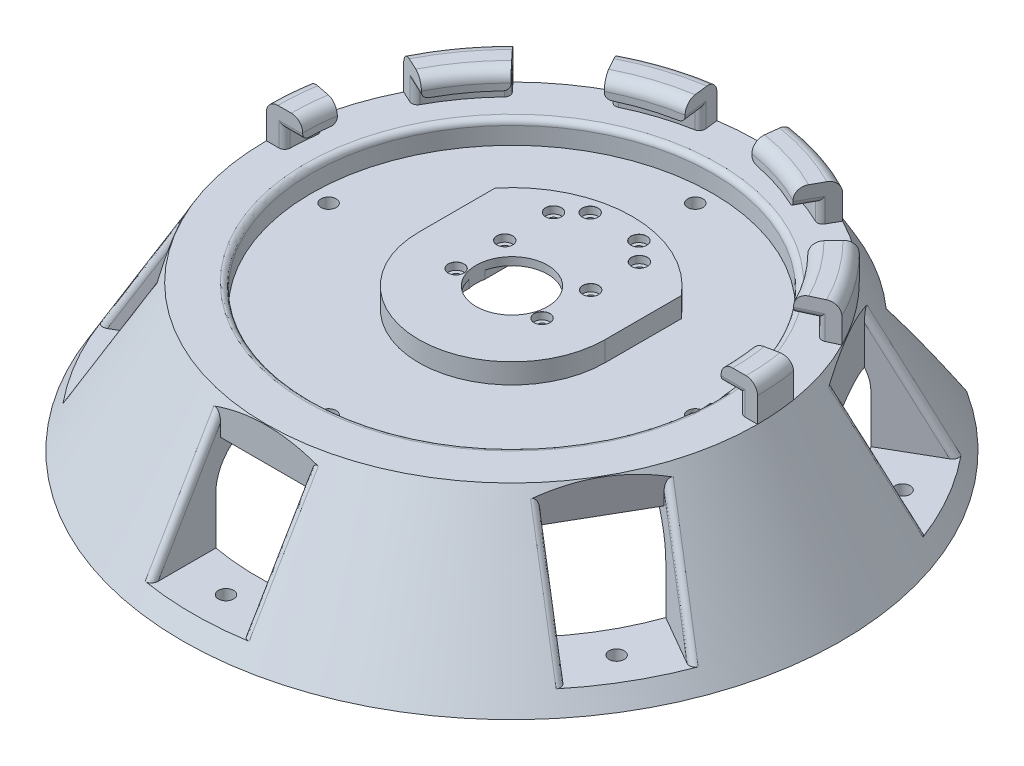
SolidWorks part; units mm, degrees
note: The reader was unsure of these and kept them because the rebuilt part matched: shared geometry of "Sketch3<3>".
material "PLA"
ref_plane "Front Plane" through (0, 0, 0) normal (0, 0, 1) x (1, 0, 0)
ref_plane "Top Plane" through (0, 0, 0) normal (0, 1, 0) x (1, 0, 0)
ref_plane "Right Plane" through (0, 0, 0) normal (1, 0, 0) x (0, 0, -1)
sketch "Sketch1" plane through (0, 0, 0) normal (0, 0, 1) x (1, 0, 0)
  line L0 (0, 0) -> (-85.725, 0)
  line L1 (-85.725, 0) -> (-115.0544, -50.8)
  line L2 (-115.0544, -50.8) -> (0, -50.8)
  line L6 (0, 0) -> (0, -50.8) construction
  line L7 (0, 0) -> (0, -50.8)
  dimension "D1" = 85.725
  dimension "D3" = 50.8
  dimension "D4" = 60
revolve "Revolve1" add sketch "Sketch1" angle 360 about L6
sketch "Sketch2" plane through (0, 0, 0) normal (0, 1, 0) x (1, 0, 0)
  circle A0 centre (0, 0) radius 12.5
  dimension "D1" = 25
extrude "Cut-Extrude1" cut sketch "Sketch2" against normal through all
sketch "Sketch3" plane through (0, 0, 0) normal (0, 1, 0) x (1, 0, 0)
  line L0 (-32.5, 0) -> (-32.5, 26.6036)
  line L1 (-32.5, 26.6036) -> (32.5, 26.6036)
  line L2 (32.5, 26.6036) -> (32.5, 0)
  circle A0 centre (0, 0) radius 32.5
  circle A1 centre (0, 0) radius 70
  circle A2 centre (0, 0) radius 42
  circle M1 centre (0, 0) radius 12.5
  dimension "D1" = 65
  dimension "D2" = 140
  dimension "D3" = 84
extrude "Cut-Extrude2" cut sketch "Sketch3" against normal blind 8 contours A1 A0 L0 L1 L2 | A1 A2
sketch "Sketch7" plane through (0, -50.8, 0) normal (0, -1, 0) x (1, 0, 0)
  line L0 (0, 88.9) -> (0, -161.1) construction
  line L1 (-85.4, 0) -> (85.4, 0) construction
  line L2 (-60, -65.5989) -> (-60, -161.1)
  line L3 (-60, -161.1) -> (60, -161.1)
  line L4 (60, -161.1) -> (60, -65.5989)
  line L5 (-60, -65.5989) -> (60, -65.5989) construction
  arc A2 (60, -65.5989) -> (-60, -65.5989) centre (0, 0) ccw
  dimension "D1" = 177.8
  dimension "D2" = 25.4
  dimension "D3" = 25.4
  dimension "D4" = 120
  dimension "D5" = 250
extrude "Cut-Extrude5" cut sketch "Sketch7" against normal blind 39 contours L3 L4 A2 L2
sketch "Sketch8" plane through (0, 0, 0) normal (0, 1, 0) x (1, 0, 0)
  line L0 (0, 0) -> (0, -115.0544) construction
  line L2 (-15.875, -123.925) -> (15.875, -123.925)
  line L3 (-15.875, -123.925) -> (-15.875, -85.825)
  line L4 (-15.875, -85.825) -> (15.875, -85.825)
  line L5 (15.875, -123.925) -> (15.875, -85.825)
  line L6 (-15.875, -123.925) -> (15.875, -85.825) construction
  line L7 (-15.875, -85.825) -> (15.875, -123.925) construction
  arc A0 (-60, 98.1708) -> (60, 98.1708) centre (0, 0) ccw construction
  point P6 (0, -104.875)
  dimension "D1" = 85.825
  dimension "D2" = 38.1
  dimension "D3" = 31.75
extrude "Cut-Extrude6" cut sketch "Sketch8" against normal blind 44.45
pattern_circular "CirPattern2" count 6 over 360 about axis through (0, 0, 0) along (0, 1, 0) of "Cut-Extrude6"
sketch "Sketch9" plane through (0, 0, 0) normal (0, 1, 0) x (1, 0, 0)
  line L0 (0, 0) -> (0, -115.0544) construction
  arc A0 (-60, 98.1708) -> (60, 98.1708) centre (0, 0) ccw construction
  circle A1 centre (0, -99.8144) radius 2.65
  dimension "D1" = 5.3
  dimension "D2" = 15.24
extrude "Cut-Extrude7" cut sketch "Sketch9" against normal through all
pattern_circular "CirPattern3" count 6 over 360 about axis through (0, 0, 0) along (0, 1, 0) of "Cut-Extrude7"
sketch "Sketch12" plane through (0, 0, 0) normal (0, 0, 1) x (1, 0, 0)
  line L0 (85.725, 0) -> (85.725, 12.7)
  line L1 (85.725, 12.7) -> (73.025, 12.7)
  line L2 (73.025, 12.7) -> (73.025, 6.35)
  line L3 (73.025, 6.35) -> (79.375, 6.35)
  line L4 (79.375, 6.35) -> (79.375, 0)
  line L5 (85.725, 0) -> (-85.725, 0) construction
  line L6 (0, 0) -> (0, 12.7) construction
  line L7 (12.5, 0) -> (-12.5, 0) construction
  line L8 (79.375, 0) -> (85.725, 0)
  point P13 (0, 6.35)
  dimension "D1" = 6.35
  dimension "D2" = 73.025
  dimension "D3" = 79.375
  dimension "D4" = 12.7
  dimension "D5" = 12.7
revolve "Revolve2" add sketch "Sketch12" angle 180 about L6
sketch "Sketch15" plane through (0, -11.8, 0) normal (0, -1, 0) x (1, 0, 0)
  line L0 (0, -1000) -> (0, 49000) construction
  point P1 (-15, 4.5)
  point P4 (-15, -12.5)
  point P5 (-15, -29.5)
  point P6 (-8.5, -35.8)
  point P7 (8.5, -35.8)
  point P8 (15, -29.5)
  point P9 (15, -12.5)
  point P10 (15, 4.5)
  dimension "D1" = 17
  dimension "D2" = 17
  dimension "D3" = 4.5
  dimension "D4" = 15
  dimension "D5" = 8.5
  dimension "D6" = 35.8
sketch "Sketch18" plane through (0, 12.7, 0) normal (0, 1, 0) x (1, 0, 0)
  line L0 (46.6433, 89.7185) -> (70.9138, 72.0849)
  line L1 (0, 201000) -> (0, -249000) construction
  line L2 (-15, 100) -> (-9, 50)
  line L3 (-9, 50) -> (9, 50)
  line L4 (9, 50) -> (15, 100)
  line L5 (-15, 100) -> (15, 100)
  line L6 (36.6704, 35.1608) -> (70.9138, 72.0849)
  line L7 (22.1081, 45.7409) -> (36.6704, 35.1608)
  line L8 (46.6433, 89.7185) -> (22.1081, 45.7409)
  line L9 (90.4704, 45.1675) -> (99.7409, 16.6359)
  line L10 (50.334, 6.8913) -> (99.7409, 16.6359)
  line L11 (44.7717, 24.0104) -> (50.334, 6.8913)
  line L12 (90.4704, 45.1675) -> (44.7717, 24.0104)
  line L13 (99.7409, -16.6359) -> (90.4704, -45.1675)
  line L14 (44.7717, -24.0104) -> (90.4704, -45.1675)
  line L15 (50.334, -6.8913) -> (44.7717, -24.0104)
  line L16 (99.7409, -16.6359) -> (50.334, -6.8913)
  line L17 (70.9138, -72.0849) -> (46.6433, -89.7185)
  line L18 (22.1081, -45.7409) -> (46.6433, -89.7185)
  line L19 (36.6704, -35.1608) -> (22.1081, -45.7409)
  line L20 (70.9138, -72.0849) -> (36.6704, -35.1608)
  line L21 (15, -100) -> (-15, -100)
  line L22 (-9, -50) -> (-15, -100)
  line L23 (9, -50) -> (-9, -50)
  line L24 (15, -100) -> (9, -50)
  line L25 (-46.6433, -89.7185) -> (-70.9138, -72.0849)
  line L26 (-36.6704, -35.1608) -> (-70.9138, -72.0849)
  line L27 (-22.1081, -45.7409) -> (-36.6704, -35.1608)
  line L28 (-46.6433, -89.7185) -> (-22.1081, -45.7409)
  line L29 (-90.4704, -45.1675) -> (-99.7409, -16.6359)
  line L30 (-50.334, -6.8913) -> (-99.7409, -16.6359)
  line L31 (-44.7717, -24.0104) -> (-50.334, -6.8913)
  line L32 (-90.4704, -45.1675) -> (-44.7717, -24.0104)
  line L33 (-99.7409, 16.6359) -> (-90.4704, 45.1675)
  line L34 (-44.7717, 24.0104) -> (-90.4704, 45.1675)
  line L35 (-50.334, 6.8913) -> (-44.7717, 24.0104)
  line L36 (-99.7409, 16.6359) -> (-50.334, 6.8913)
  line L37 (-70.9138, 72.0849) -> (-46.6433, 89.7185)
  line L38 (-22.1081, 45.7409) -> (-46.6433, 89.7185)
  line L39 (-36.6704, 35.1608) -> (-22.1081, 45.7409)
  line L40 (-70.9138, 72.0849) -> (-36.6704, 35.1608)
  point P4 (0, 50)
  point P7 (0, 100)
  point P48 (0, 0)
  dimension "D1" = 18
  dimension "D2" = 50
  dimension "D3" = 30
  dimension "D4" = 50
  dimension "D5" = 10
extrude "Cut-Extrude9" cut sketch "Sketch18" against normal blind 12.7
sketch "Sketch20" plane through (0, -11.8, 0) normal (0, -1, 0) x (1, 0, 0)
  line L0 (-22.5, -33) -> (-12.5, -40)
  line L1 (22.5, 20) -> (-22.5, 20)
  line L2 (22.5, 20) -> (22.5, -40)
  line L3 (22.5, -40) -> (-22.5, -40)
  line L4 (-22.5, 20) -> (-22.5, -40)
  line L5 (22.5, 20) -> (-22.5, -40) construction
  line L6 (22.5, -40) -> (-22.5, 20) construction
  line L7 (-12.5, -40) -> (12.5, -40)
  line L8 (12.5, -40) -> (22.5, -33)
  point P0 (0, -10)
  dimension "D1" = 60
  dimension "D2" = 45
  dimension "D3" = 10
  dimension "D4" = 10
  dimension "D5" = 7
  dimension "D6" = 7
  dimension "D7" = 10
extrude "Cut-Extrude11" cut sketch "Sketch3<3>" against normal blind 1 contours A0 L1 M1 | A0 L1 L0 | L1 A0 | L1 A2 A0 | A0 L2 L1
sketch "Sketch3<3>" plane through (0, 0, 0) normal (0, 1, 0) x (1, 0, 0) same geometry as "Sketch3"
sketch "Sketch22" plane through (0, -1, 0) normal (0, 1, 0) x (1, 0, 0)
  circle A0 centre (-15, 12.5) radius 1.4
  circle A1 centre (-15, 29.5) radius 1.4
  circle A2 centre (-8.5, 35.8) radius 1.4
  circle A3 centre (8.5, 35.8) radius 1.4
  circle A4 centre (15, 29.5) radius 1.4
  circle A5 centre (15, 12.5) radius 1.4
  circle A6 centre (15, -4.5) radius 1.4
  circle A7 centre (-15, -4.5) radius 1.4
  dimension "D1" = 17
  dimension "D2" = 17
  dimension "D3" = 2.8
  dimension "D4" = 2.8
  dimension "D5" = 2.8
  dimension "D6" = 2.8
  dimension "D7" = 2.8
  dimension "D8" = 2.8
  dimension "D9" = 2.8
  dimension "D10" = 2.8
  dimension "D11" = 17
  dimension "D12" = 30
  dimension "D13" = 30
  dimension "D14" = 30
  dimension "D15" = 17
  dimension "D16" = 17
  dimension "D17" = 6.3
  dimension "D18" = 6.3
  dimension "D19" = 35.8
  dimension "D20" = 8.5
  dimension "D21" = 35.8
  dimension "D22" = 15
  dimension "D23" = 19.5256
  dimension "D24" = 15.6605
hole_wizard "CBORE for M2.5 SHCS1" positions "Sketch23" profile "Sketch24" counterbore size "M2.5" standard "ANSI Metric" end condition through all
sketch "Sketch23" plane through (0, -1, 0) normal (0, 1, 0) x (1, 0, 0)
  point P0 (-15, -4.5)
  point P3 (-15, 12.5)
  point P6 (-15, 29.5)
  point P9 (-8.5, 35.8)
  point P12 (8.5, 35.8)
  point P15 (15, 29.5)
  point P18 (15, 12.5)
  point P21 (15, -4.5)
sketch "Sketch24" plane through (-15, -1, 4.5) normal (1, 0, 0) x (0, 0, 1)
  line L0 (0, 0) -> (0, 49.8)
  line L1 (0, 49.8) -> (1.45, 49.8)
  line L3 (1.45, 49.8) -> (1.45, 2.5)
  line L4 (2.75, 2.5) -> (1.45, 2.5)
  line L5 (2.75, 2.5) -> (2.75, 0.025)
  line L6 (2.75, 0.025) -> (2.775, 0)
  line L7 (2.775, 0) -> (0, 0)
  line L8 (-2.75, 0.025) -> (-2.775, 0) construction
  line L11 (0, -6.35) -> (0, 107.95) construction
  dimension "Thru Hole Dia." = 2.9
  dimension "Thru Hole Depth" = 49.8
  dimension "C'Bore Dia." = 5.5
  dimension "C'Bore Depth" = 2.5
  dimension "Near C'Sink Dia." = 5.55
  dimension "Near C'Sink Angle" = 90
fillet "Fillet1" radius 4 12 edges at (85.4509, 12.7, -6.8497) (69.353, 12.7, -50.3879) (26.4905, 12.7, -81.5293) (-26.4905, 12.7, -81.5293) (-69.353, 12.7, -50.3879) (-85.4509, 12.7, -6.8497) (-72.8088, 12.7, -5.6148) (-59.0785, 12.7, -42.923) (-22.566, 12.7, -69.4509) (22.566, 12.7, -69.4509) (59.0785, 12.7, -42.923) (72.8088, 12.7, -5.6148)
fillet "Fillet2" radius 2 12 edges at (75.2789, 6.35, -11.8112) (76.2, 6.35, 0) (53.9595, 6.35, -53.8033) (67.8444, 6.35, -34.6924) (12.0293, 6.35, -75.2444) (34.4956, 6.35, -67.9447) (-12.0293, 6.35, -75.2444) (-34.4956, 6.35, -67.9447) (-53.9595, 6.35, -53.8033) (-67.8444, 6.35, -34.6924) (-75.2789, 6.35, -11.8112) (-76.2, 6.35, 0)
fillet "Fillet3" radius 2 12 edges at (-78.3963, 4.175, -12.4261) (-56.1201, 4.175, -56.1331) (-70.7278, 4.175, -36.0273) (-12.4079, 4.175, -78.3992) (56.1201, 4.175, -56.1331) (78.3963, 4.175, -12.4261) (-79.375, 4.175, 0) (-36.0437, 4.175, -70.7195) (12.4079, 4.175, -78.3992) (36.0437, 4.175, -70.7195) (70.7278, 4.175, -36.0273) (79.375, 4.175, 0)
fillet "Fillet4" radius 2 10 edges
fillet "Fillet5" radius 2 1 edges at (0, 0, 70)
fillet "Fillet6" radius 16 4 edges at (88.9, -11.8, 0) (-88.9, -11.8, 0) (-44.45, -11.8, 76.9897) (44.45, -11.8, 76.9897)
fillet "Fillet7" radius 16 1 edges at (64.036, -11.8, -61.6652)
fillet "Fillet8" radius 16 1 edges at (-64.036, -11.8, -61.6652)
fillet "Fillet9" radius 1 2 edges
sketch "Sketch28" plane through (0, -11.8, 0) normal (0, -1, 0) x (1, 0, 0)
  line L0 (9.2, 12) -> (-9.2, 12)
  line L1 (-12.2, 9) -> (-12.2, -30)
  line L2 (-9.2, -33) -> (9.2, -33)
  line L3 (12.2, -30) -> (12.2, 9)
  arc A0 (-9.2, 12) -> (-12.2, 9) centre (-9.2, 9) ccw
  arc A1 (-12.2, -30) -> (-9.2, -33) centre (-9.2, -30) ccw
  arc A2 (9.2, -33) -> (12.2, -30) centre (9.2, -30) ccw
  arc A3 (12.2, 9) -> (9.2, 12) centre (9.2, 9) ccw
extrude "Cut-Extrude12" cut sketch "Sketch28" against normal offset from surface (8.05 mm away) 2.75
extrude "Cut-Extrude15" cut sketch "Sketch20" against normal offset from surface (5.3 mm away) 2.75
sketch "Sketch29" plane through (0, -8, 0) normal (0, 1, 0) x (1, 0, 0)
  point P0 (0, 64)
  point P5 (64, 0)
  point P6 (0, -64)
  point P7 (-64, 0)
  point P8 (0, 0)
  dimension "D1" = 64
  dimension "D2" = 4
hole_wizard "M5 Clearance Hole1" positions "Sketch32" profile "Sketch33" hole size "M5" standard "ANSI Metric" end condition up to next
sketch "Sketch32" plane through (0, -8, 0) normal (0, 1, 0) x (1, 0, 0)
  point P0 (0, 64)
  point P3 (64, 0)
  point P6 (0, -64)
  point P9 (-64, 0)
sketch "Sketch33" plane through (0, -8, -64) normal (1, 0, 0) x (0, 0, 1)
  line L0 (0, 0) -> (0, 3.8)
  line L1 (0, 3.8) -> (2.65, 3.8)
  line L2 (2.65, 3.8) -> (2.65, 0)
  line L5 (2.65, 0) -> (0, 0)
  line L11 (0, -6.35) -> (0, 107.95) construction
  dimension "Thru Hole Dia." = 5.3
  dimension "Thru Hole Depth" = 3.8
